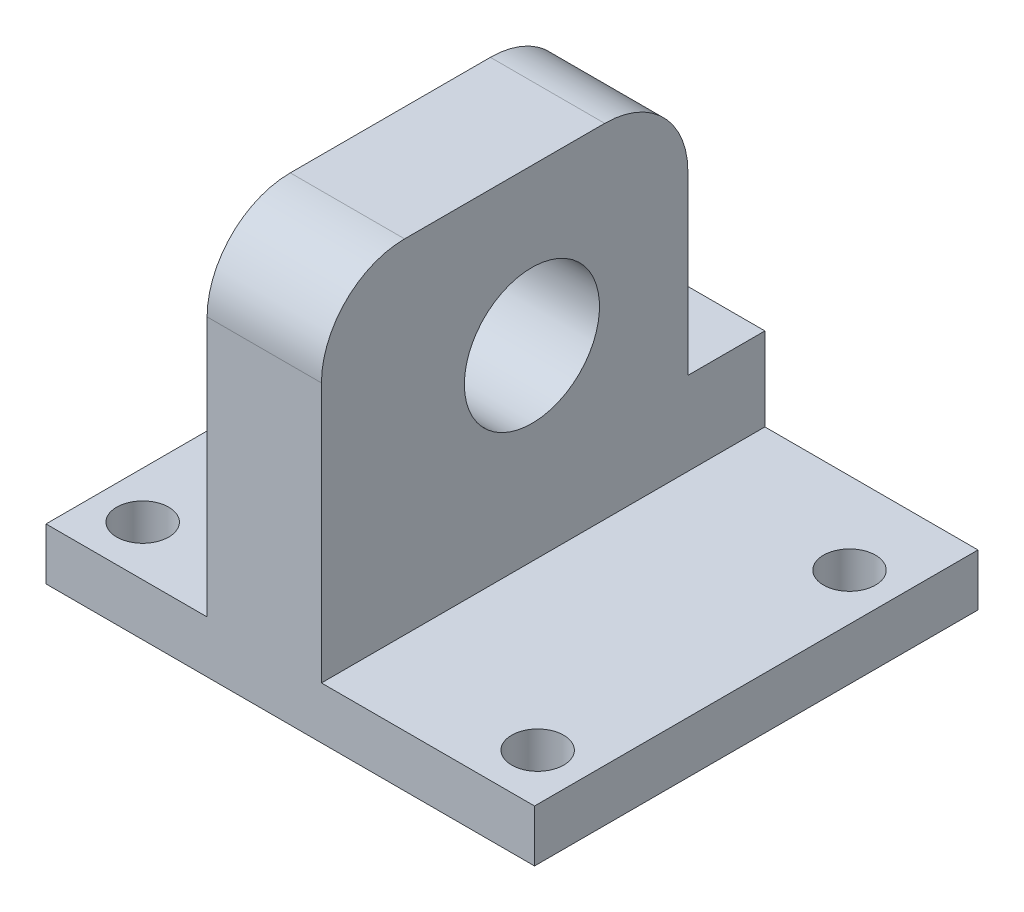
SolidWorks part; units mm, degrees
ref_plane "前视基准面" through (0, 0, 0) normal (0, 0, 1) x (1, 0, 0)
ref_plane "上视基准面" through (0, 0, 0) normal (0, 1, 0) x (1, 0, 0)
ref_plane "右视基准面" through (0, 0, 0) normal (1, 0, 0) x (0, 0, -1)
other "Configuration Table"
sketch "草图1" plane through (0, 0, 0) normal (0, 1, 0) x (1, 0, 0)
  line L1 (23.5, -12.9607) -> (-23.5, -12.9607)
  line L2 (23.5, -12.9607) -> (23.5, 29.7046)
  line L3 (23.5, 29.7046) -> (-23.5, 29.7046)
  line L4 (-23.5, -12.9607) -> (-23.5, 29.7046)
  circle A0 centre (-19, 21.8424) radius 2.5
  circle A1 centre (19, 21.8424) radius 2.5
  circle A2 centre (-19, -8.1576) radius 2.5
  circle A3 centre (19, -8.1576) radius 2.5
  point P0 (0, 0)
  dimension "D2" = 5
  dimension "D3" = 5
  dimension "D4" = 5
  dimension "D5" = 5
  dimension "D1" = 47
  dimension "D6" = 7.8621
extrude "凸台-拉伸1" add sketch "草图1" along normal blind 5 contours L4 L1 L2 L3 A3 A2 A1 A0 region at (0, 0, -8.4343)
sketch "草图2" plane through (0, 5, 0) normal (0, 1, 0) x (1, 0, 0)
  line L0 (23.5, 29.7046) -> (-23.5, 29.7046) construction
  line L1 (3, -12.9607) -> (-3, -12.9607)
  line L2 (3, -12.9607) -> (3, 29.7046)
  line L3 (3, 29.7046) -> (-3, 29.7046)
  line L4 (-3, -12.9607) -> (-3, 29.7046)
  line L5 (3, -12.9607) -> (-3, 29.7046) construction
  line L6 (3, 29.7046) -> (-3, -12.9607) construction
  line L7 (23.5, -12.9607) -> (-23.5, -12.9607) construction
  line L8 (0, 8.3719) -> (0, 0)
  line L9 (23.5, -12.9607) -> (23.5, 29.7046) construction
  line L10 (-23.5, 29.7046) -> (23.5, 29.7046)
  line L11 (-23.5, 29.7046) -> (-23.5, 27.7046)
  line L12 (-23.5, 27.7046) -> (23.5, 27.7046)
  line L13 (23.5, 29.7046) -> (23.5, 27.7046)
  point P0 (0, 8.3719)
  line M10 (-23.5, 29.7046) -> (-23.5, -12.9607)
  line M12 (23.5, -12.9607) -> (23.5, 29.7046)
  line M13 (23.5, 29.7046) -> (-23.5, 29.7046)
  dimension "D1" = 6
  dimension "D2" = 2
extrude "凸台-拉伸2" add sketch "草图2" along normal blind 33 contours L12 L4 L2 | L12 L4 M10 M13 | L2 L12 M12 M13 | L4 L12 L2 M13 region at (0, 5, 12.5497) region at (0, 5, -28.7046) region at (13.25, 5, -28.7046) region at (-13.25, 5, -28.7046)
sketch "草图3" plane through (-3, 0, 0) normal (-1, 0, 0) x (0, 0, 1)
  line L0 (-27.7046, 5) -> (12.9607, 5)
  line M3 (12.9607, 5) -> (12.9607, 38)
  line M4 (12.9607, 38) -> (-27.7046, 38)
  line M5 (-27.7046, 38) -> (-27.7046, 5)
extrude "凸台-拉伸3" add sketch "草图3" against normal up to surface (6 mm away) contours M4 | M4 | M4 | M4 | M4 | M3 M4 | M5 M4 | M4 M5 region at (-3, 21.5, -7.3719) up to face at (3, 21.5, -7.3719)
sketch "草图4" plane through (-3, 2.1172, 0) normal (-1, 0, 0) x (0, 0, 1)
  line L12 (-27.6221, 2.1767) -> (13.0432, 2.1767)
  line L13 (13.0432, 2.1767) -> (13.0432, 20.1767)
  line L16 (-29.6221, 20.1767) -> (-27.6221, 20.1767)
  line L17 (-27.6221, 20.1767) -> (-27.6221, 2.1767)
  line L18 (13.0432, 20.1767) -> (-2.9362, 26.9857)
  line L21 (-10.6523, 27.5823) -> (-29.6221, 20.1767)
  circle A0 centre (-7.2895, 20.8784) radius 6.5
  arc A5 (-2.9362, 26.9857) -> (-10.6523, 27.5823) centre (-7.2895, 20.8784) ccw
  dimension "D2" = 13
extrude "切除-拉伸2" cut sketch "草图4" against normal blind 7 contours A0 | A0 region at (-3, 22.9956, -7.2895)
chamfer "倒角1" distance 3 angle 45 2 edges at (23.5, 38, -28.7046) (-23.5, 38, -28.7046)
sketch "草图6" plane through (0, 38, 0) normal (0, 1, 0) x (1, 0, 0)
  line L0 (-3, 21.5525) -> (28.9873, 21.5525)
  line L1 (-3, -12.9607) -> (-3, 27.7046) construction
  line L2 (28.9873, 21.5525) -> (28.9873, 31.4157)
  line L3 (28.9873, 31.4157) -> (-26.3946, 31.4157)
  line L4 (-26.3946, 31.4157) -> (-26.3946, 21.5525)
  line L5 (-26.3946, 21.5525) -> (-3, 21.5525)
  line L10 (-26.3946, 22.2925) -> (28.9873, 22.2925)
  line L11 (-26.3946, 22.2925) -> (-26.3946, 21.5525)
  line M6 (3, 27.7046) -> (20.5, 27.7046)
  line M7 (20.5, 27.7046) -> (20.5, 29.7046)
  line M8 (20.5, 29.7046) -> (-20.5, 29.7046)
  line M9 (-20.5, 29.7046) -> (-20.5, 27.7046)
  line M10 (-20.5, 27.7046) -> (-3, 27.7046)
  line M11 (-3, 27.7046) -> (-3, -12.9607)
  line M13 (3, -12.9607) -> (3, 27.7046)
  dimension "D1" = 0.74
extrude "切除-拉伸8" cut sketch "草图6" against normal blind 25 contours L4 L10 L2 L3 M11 M10 M9 M8 M7 M6 M13 | L10 M11 M13 M6 M7 M8 M9 M10 region at (0, 38, -27.6533) region at (-14.6973, 38, -22.8538)
fillet "圆角3" radius 8 2 edges at (0, 38, -22.2925) (0, 38, 12.9607)
sketch "草图7" plane through (0, 0, -27.7046) normal (0, 0, 1) x (1, 0, 0)
  line L4 (23.5, 13) -> (3, 13)
  line L5 (3, 13) -> (3, 5)
  line L6 (3, 5) -> (23.5, 5)
  line L7 (23.5, 5) -> (23.5, 13)
  line L8 (23.5, 13) -> (3, 13)
  line L9 (3, 13) -> (3, 5)
  line L10 (3, 5) -> (23.5, 5)
  line L11 (23.5, 5) -> (23.5, 13)
  dimension "D1" = 0
extrude "切除-拉伸9" cut sketch "草图7" against normal blind 10
sketch "草图8" plane through (-3, 0, 0) normal (-1, 0, 0) x (0, 0, 1)
  line L6 (4.9607, 38) -> (-14.2925, 38)
  line L7 (4.9607, 38) -> (-14.2925, 38)
  line L10 (-22.2925, 30) -> (-22.2925, 13)
  line L11 (-22.2925, 13) -> (-27.7046, 13)
  line L12 (-27.7046, 13) -> (-27.7046, 5)
  line L13 (-27.7046, 5) -> (12.9607, 5)
  line L14 (12.9607, 5) -> (12.9607, 30)
  line L18 (-22.2925, 30) -> (-22.2925, 13)
  line L19 (-22.2925, 13) -> (-27.7046, 13)
  line L20 (-27.7046, 13) -> (-27.7046, 5)
  line L21 (-27.7046, 5) -> (12.9607, 5)
  line L22 (12.9607, 5) -> (12.9607, 30)
  circle A0 centre (-7.2895, 22.9956) radius 6.5 construction
  circle A1 centre (-7.2895, 22.9956) radius 6.5
  arc A3 (-14.2925, 38) -> (-22.2925, 30) centre (-14.2925, 30) ccw
  arc A5 (-14.2925, 38) -> (-22.2925, 30) centre (-14.2925, 30) ccw
  arc A7 (12.9607, 30) -> (4.9607, 38) centre (4.9607, 30) ccw
  arc A8 (12.9607, 30) -> (4.9607, 38) centre (4.9607, 30) ccw
  dimension "D1" = 0
extrude "凸台-拉伸4" add sketch "草图8" along normal blind 5
fillet "圆角4" radius 2 1 edges at (-8, 9, -27.7046)
